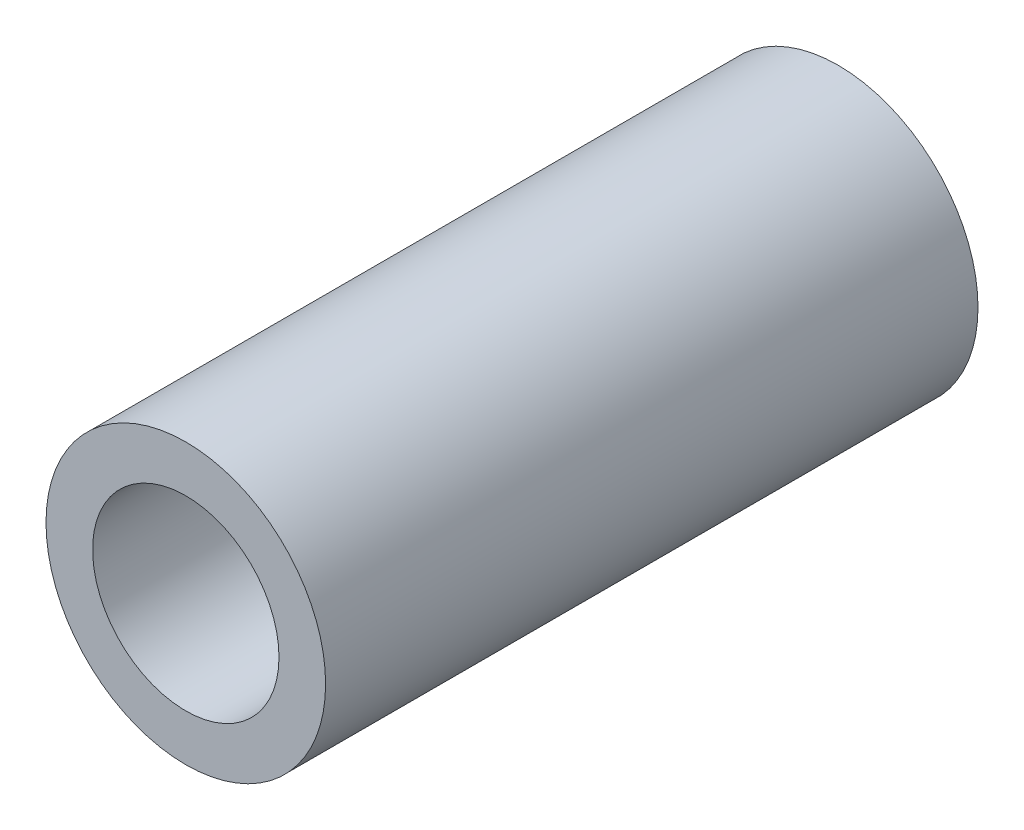
SolidWorks part; units mm, degrees
material "Brass"
ref_plane "Front Plane" through (0, 0, 0) normal (0, 0, 1) x (1, 0, 0)
ref_plane "Top Plane" through (0, 0, 0) normal (0, 1, 0) x (1, 0, 0)
ref_plane "Right Plane" through (0, 0, 0) normal (1, 0, 0) x (0, 0, -1)
sketch "Sketch1" plane through (0, 0, 0) normal (0, 0, 1) x (1, 0, 0)
  circle A0 centre (0, 0) radius 3
  circle A1 centre (0, 0) radius 2
  dimension "D1" = 6
  dimension "D2" = 4
extrude "Boss-Extrude1" add sketch "Sketch1" along normal blind 14
